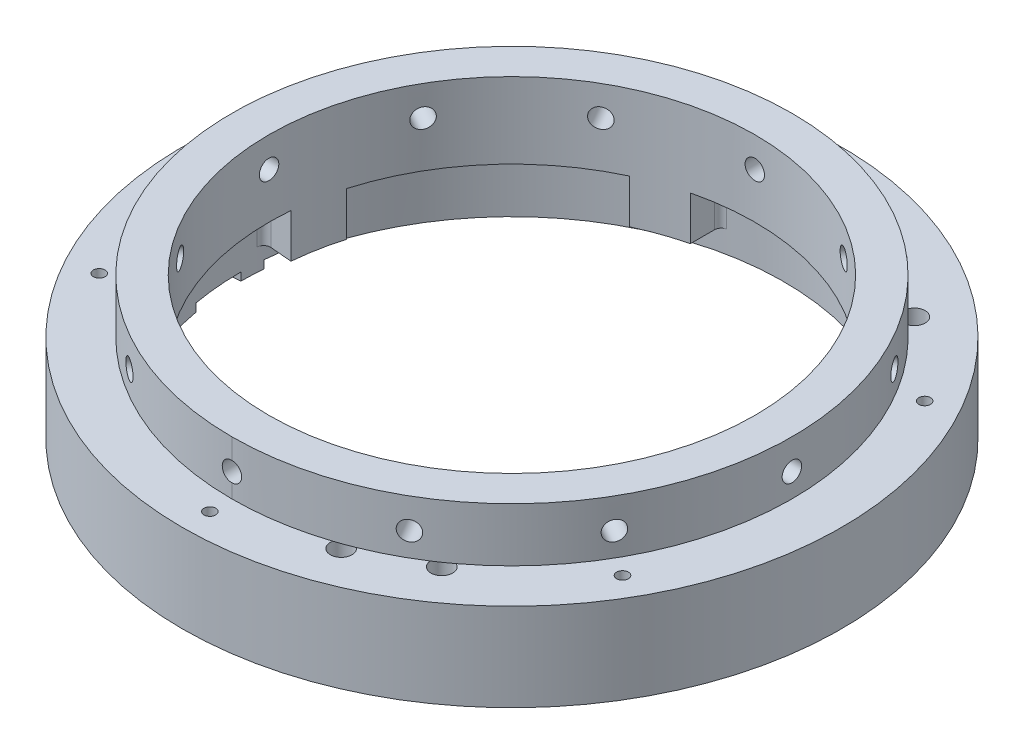
SolidWorks part; units mm, degrees
ref_plane "Front Plane" through (0, 0, 0) normal (0, 0, 1) x (1, 0, 0)
ref_plane "Top Plane" through (0, 0, 0) normal (0, 1, 0) x (1, 0, 0)
ref_plane "Right Plane" through (0, 0, 0) normal (1, 0, 0) x (0, 0, -1)
sketch "Sketch1" plane through (0, 0, 0) normal (0, 1, 0) x (1, 0, 0)
  circle A0 centre (0, 0) radius 64.77
  circle A1 centre (0, 0) radius 76.2
  circle A2 centre (0, 0) radius 56.1975
  circle A4 centre (0, 0) radius 62.865
  dimension "D1" = 152.4
  dimension "D3" = 112.395
  dimension "D2" = 129.54
  dimension "D4" = 13.335
extrude "Boss-Extrude1" add sketch "Sketch1" along normal blind 17.526 contours A0 A2 | A0 A4 region at (-62.938, 0, 0) region at (-61.0869, 0, 0)
extrude "Boss-Extrude2" add sketch "Sketch1<4>" along normal blind 5.08 and the other way blind 15.24 contours A1 A0 | A0 A4 region at (-62.938, 0, 0) region at (-74.0447, 0, 0)
sketch "Sketch1<4>" plane through (0, 0, 0) normal (0, 1, 0) x (1, 0, 0) same geometry as "Sketch1"
sketch "Sketch3" plane through (0, -15.24, 0) normal (0, -1, 0) x (1, 0, 0)
  line L0 (0, 0) -> (-65.7887, 5.7558) construction
  line L1 (0, 0) -> (0, 69.85) construction
  line L2 (0, 0) -> (48.9804, 58.3726)
  line L3 (0, 0) -> (13.232, 75.0424)
  line L4 (-13.335, -54.5925) -> (-13.335, -60.117)
  line L5 (13.335, -54.5925) -> (13.335, -60.117)
  line L6 (-13.335, -60.117) -> (13.335, -60.117)
  line L7 (-13.335, -60.117) -> (-13.335, -61.4344)
  line L8 (-23.7501, -50.9322) -> (-26.5679, -56.975)
  line L9 (0, 0) -> (-23.7501, -50.9322) construction
  line L10 (-65.2934, 11.4174) -> (-61.874, 11.1182)
  line L11 (-66.284, 0.0941) -> (-62.8647, -0.205)
  line L12 (-66.0236, -5.8708) -> (-62.6433, -5.2748)
  line L13 (-64.0498, -17.0646) -> (-60.6695, -16.4686)
  line L14 (-65.0367, -11.4677) -> (0, 0) construction
  line L15 (27.9275, 60.1135) -> (26.7536, 56.8881)
  line L16 (17.2465, 64.0011) -> (16.0725, 60.7757)
  line L17 (38.0961, -54.2427) -> (35.8898, -51.6133)
  line L18 (46.8033, -46.9365) -> (44.597, -44.3071)
  circle A0 centre (-65.7887, 5.7558) radius 5.6833
  circle A1 centre (0, 69.85) radius 1.3589
  circle A2 centre (0, 0) radius 76.2 construction
  circle A5 centre (0, 0) radius 56.1975 construction
  arc A7 (-26.5679, -56.975) -> (-13.335, -61.4344) centre (0, 0) ccw
  arc A9 (-23.7501, -50.9322) -> (-13.335, -54.5925) centre (0, 0) ccw
  circle A10 centre (-65.7887, 5.7558) radius 2.5083
  circle A11 centre (-65.0367, -11.4677) radius 5.6832
  circle A12 centre (0, 0) radius 62.865 construction
  circle A13 centre (-65.0367, -11.4677) radius 2.5082
  circle A14 centre (0, 0) radius 62.865 construction
  circle A15 centre (22.587, 62.0573) radius 5.6832
  circle A16 centre (22.587, 62.0573) radius 2.5082
  circle A17 centre (42.4497, -50.5896) radius 5.6832
  circle A18 centre (42.4497, -50.5896) radius 2.5082
  arc A19 (-62.6433, -5.2748) -> (-60.6695, -16.4686) centre (0, 0) ccw
  point P0 (0, -60.117)
  point P38 (0, 0)
  point P56 (0, 0)
  circle M49 centre (0, 0) radius 62.865
  dimension "D4" = 11.3665
  dimension "D5" = 2.7178
  dimension "D11" = 5.0165
  dimension "D1" = 66.04
  dimension "D2" = 85
  dimension "D3" = 69.85
  dimension "D6" = 30
  dimension "D7" = 10
  dimension "D9" = 26.67
  dimension "D8" = 5.5245
  dimension "D10" = 25
  dimension "D13" = 15
  dimension "D12" = 2
  dimension "D14" = 3
extrude "Cut-Extrude1" cut sketch "Sketch3" against normal blind 1.8415 contours A11 A13 M49 | A11 L13 M49 | A13 | A11 L12 M49 | A0 A10 M49 | A10 | A0 L11 M49 | A0 L10 M49 region at (-62.774, -15.24, 10.8743) region at (-63.6243, -15.24, 10.8507) region at (-63.7086, -15.24, 0.1915) region at (-63.4495, -15.24, -5.7433) region at (-64.265, -15.24, -5.9885) region at (-61.5874, -15.24, -16.304) region at (-65.7887, -15.24, 5.7558) region at (-65.0367, -15.24, -11.4677)
extrude "Cut-Extrude2" cut sketch "Sketch3<3>" against normal up to surface (20.32 mm away) contours A1 region at (0, -15.24, 69.85) up to face at (0, 5.08, 64.77)
sketch "Sketch3<3>" plane through (0, -15.24, 0) normal (0, -1, 0) x (1, 0, 0) same geometry as "Sketch3"
sketch "Sketch6" plane through (0, -13.3985, 0) normal (0, -1, 0) x (1, 0, 0)
  line L0 (-65.0367, -11.4677) -> (0, 0) construction
  line L1 (0, 0) -> (-65.7887, 5.7558) construction
  arc A0 (-65.2934, 11.4174) -> (-66.284, 0.0941) centre (-65.7887, 5.7558) ccw construction
  arc A1 (-65.2934, 11.4174) -> (-66.284, 0.0941) centre (-65.7887, 5.7558) ccw
  circle A2 centre (-65.7887, 5.7558) radius 2.5083
  circle A3 centre (-65.0367, -11.4677) radius 2.5082
  point P9 (0, 0)
  dimension "D1" = 5.0165
  dimension "D3" = 15
  dimension "D2" = 2
extrude "Cut-Extrude4" cut sketch "Sketch6" against normal up to surface (18.4785 mm away) contours A2 | A3 region at (-65.7887, -13.3985, 5.7558) up to face at (0, 5.08, 71.2089)
pattern_circular "CirPattern1" count 3 over 360 about axis through (0, -15.24, 0) along (0, 1, 0) of "Cut-Extrude1", "Cut-Extrude4"
pattern_circular "CirPattern2" count 6 over 360 about axis through (0, -15.24, 0) along (0, 1, 0) of "Cut-Extrude2"
ref_plane "Plane1" through (0, 0, 76.2) normal (0, 0, 1) x (1, 0, 0)
sketch "Sketch5" plane through (0, 0, 76.2) normal (0, 0, 1) x (1, 0, 0)
  line L0 (0, -15.24) -> (0, 10.5664) construction
  line L1 (-1.3589, -15.24) -> (1.3589, -15.24) construction
  line L3 (-76.2, -15.24) -> (76.2, -15.24) construction
  line L4 (76.2, 5.08) -> (-76.2, 5.08) construction
  line L5 (-76.2, -15.24) -> (76.2, -15.24)
  line L6 (76.2, 5.08) -> (-76.2, 5.08)
  circle A0 centre (0, 10.5664) radius 2.2479
  dimension "D2" = 4.4958
  dimension "D1" = 5.4864
extrude "Cut-Extrude3" cut sketch "Sketch5" against normal up to surface (20.0475 mm away) contours A0 region at (0, 10.5664, 76.2) up to face at (0, 17.526, 56.1975)
extrude "Boss-Extrude3" add sketch "Sketch3<11>" along normal blind 10.16 from surface contours L4 A9 L8 A7 L7 starting at face at (0, 0, 56.1975)
sketch "Sketch3<11>" plane through (0, -15.24, 0) normal (0, -1, 0) x (1, 0, 0) same geometry as "Sketch3"
pattern_circular "CirPattern3" count 6 over 360 about axis through (0, 17.526, 0) along (0, 1, 0) of "Boss-Extrude3"
fillet "Fillet1" radius 1.5875 12 edges at (-62.6258, -5.08, -5.479) (-59.8713, -5.08, -19.1688) (-26.5679, -5.08, -56.975) (-13.335, -5.08, -61.4344) (36.0579, -5.08, -51.496) (46.5363, -5.08, -42.2657) (62.6258, -5.08, 5.479) (59.8713, -5.08, 19.1688) (26.5679, -5.08, 56.975) (13.335, -5.08, 61.4344) (-36.0579, -5.08, 51.496) (-46.5363, -5.08, 42.2657)
pattern_circular "CirPattern4" count 12 over 360 about axis through (0, 17.526, 0) along (0, 1, 0) of "Cut-Extrude3"
sketch "Sketch8" plane through (0, 17.526, 0) normal (0, 1, 0) x (1, 0, 0)
  arc A0 (-34.7117, -52.4129) -> (12.0518, -61.699) centre (0, 0) ccw construction
  arc A1 (-34.7117, -52.4129) -> (12.0518, -61.699) centre (0, 0) ccw
  circle A2 centre (0, 0) radius 62.865
  circle M2 centre (0, 0) radius 56.1975
extrude "Cut-Extrude5" [suppressed] cut sketch "Sketch8" against normal up to surface (17.526 mm away) contours A1 A2 M2 up to face at (42.8898, 0, 37.3465)
sketch "Sketch9" plane through (0, 0, 0) normal (0, 0, 1) x (1, 0, 0)
  line L0 (0, 5.08) -> (0, 17.526)
  line L1 (76.2, 5.08) -> (-76.2, 5.08) construction
  line L2 (64.77, 17.526) -> (-64.77, 17.526) construction
split line "Split Line2"
equation "\"Middle Coupler Inner Daimeter\"= 3.875in"
equation "\"Middle Coupler  Wall Thickness\" = 0.25in"
equation "\"Middle Coupler Bottom Thickness\"= 0.2in"
equation "\"Bearing Rail Offset\"= 0.45in"
equation "\"3-56 UNF Tap\"= 0.089in"
equation "\"3-48 Tap\"= 0.079in"
equation "\"3-56 UNF Clearance\"= 0.104in"
equation "\"3-48 Clearance\" = 0.104in"
equation "\"Ball Bearing Distance\"= 0.03in"
equation "\"TCA Outer Diameter\" = 6in"
equation "\"Interstage Aeroframe Wall Thickness\" = 0.072in"
equation "\"Compression Spring OD\"= 0.42in"
equation "\"10-24 Tap\"= 0.157in"
equation "\"10-24 Clearance\"= 0.196in"
equation "\"Lower Stage Fuselage Wall Thickness\" = 0.25in"
equation "\"6-32 Tap\" = 0.107in"
equation "\"6-32 Clearance\" = 0.144"
equation "\"1/4-20 Tap\" = 0.201in"
equation "\"12-24 Tap\" = 0.177in"
equation "\"D1@Sketch1\"=\"TCA Outer Diameter\""
equation "\"D5@Sketch3\"=\"6-32 Tap\""
equation "\"D2@Sketch5\"=\"12-24 Tap\""
equation "\"D8@Sketch3\"=3/16+0.03"
equation "\"D3@Sketch1\"=\"Middle Coupler Inner Daimeter\" + 0.55"
equation "\"D4@Sketch3\"=7/16 + 0.01"
equation "\"D1@Boss-Extrude1\"=0.15 + \"12-24 Major Diameter\"*2.5"
equation "\"12-24 Major Diameter\"= 0.216in"
equation "\"D1@Cut-Extrude1\"=1/16 + 0.01"
equation "\"D11@Sketch3\"=3/16 + 0.01"
equation "\"D1@Sketch6\"=3/16 + 0.01"
equation "\"D1@Sketch5\"=\"12-24 Major Diameter\""
